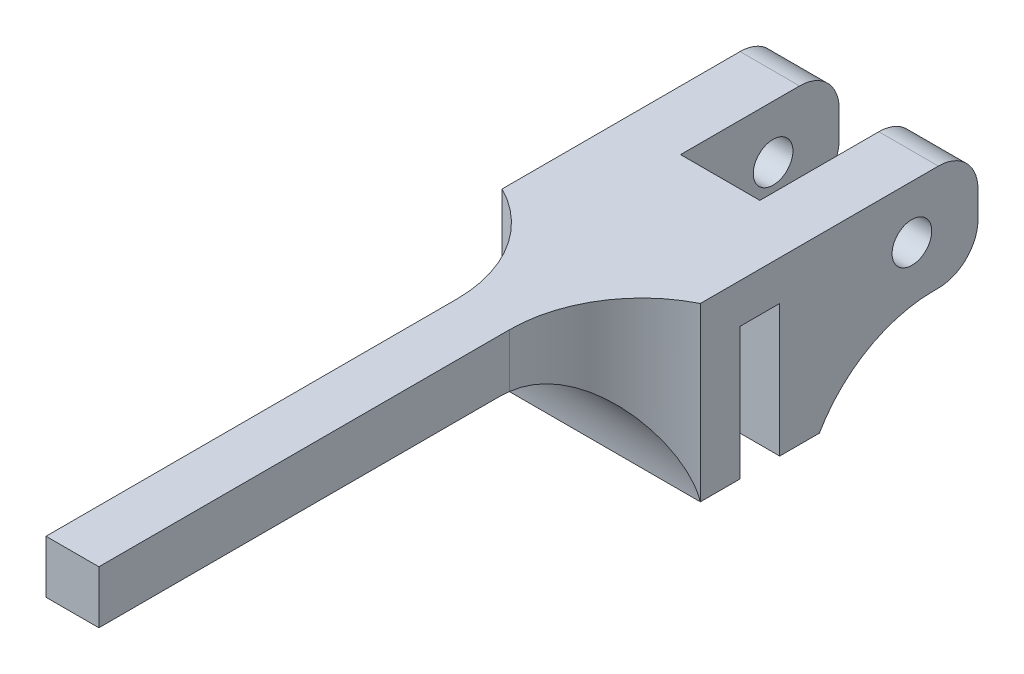
SolidWorks part; units mm, degrees
ref_plane "Alzado" through (0, 0, 0) normal (0, 0, 1) x (1, 0, 0)
ref_plane "Planta" through (0, 0, 0) normal (0, 1, 0) x (1, 0, 0)
ref_plane "Vista lateral" through (0, 0, 0) normal (1, 0, 0) x (0, 0, -1)
sketch "Croquis2" plane through (0, 0, 0) normal (0, 0, 1) x (1, 0, 0)
  line L1 (-7.5, 6.5) -> (7.5, 6.5)
  line L2 (-7.5, 6.5) -> (-7.5, -6.5)
  line L3 (-7.5, -6.5) -> (7.5, -6.5)
  line L4 (7.5, 6.5) -> (7.5, -6.5)
  point P4 (0, -6.5)
  point P6 (7.5, 0)
  dimension "D1" = 15
  dimension "D2" = 13
extrude "Saliente-Extruir1" add sketch "Croquis2" along normal mid plane 9
sketch "Croquis3" plane through (0, 0, 0) normal (0, 0, 1) x (1, 0, 0)
  line L0 (-7.5, 6.5) -> (-7.5, -6.5) construction
  line L1 (-7.5, 3.5) -> (7.5, 3.5)
  line L2 (-7.5, 3.5) -> (-7.5, -6.5)
  line L3 (-7.5, -6.5) -> (7.5, -6.5)
  line L4 (7.5, 3.5) -> (7.5, -6.5)
  line L5 (7.5, 6.5) -> (-7.5, 6.5) construction
  dimension "D1" = 3
extrude "Cortar-Extruir1" cut sketch "Croquis3" against normal mid plane 3
sketch "Croquis4" plane through (0, 0, 0) normal (0, 0, 1) x (1, 0, 0)
  line L0 (7.5, 6.5) -> (-7.5, 6.5) construction
  line L1 (-1.5, 0) -> (-1.5, -6.5)
  line L2 (-7.5, -6.5) -> (7.5, -6.5) construction
  line L3 (1.5, 0) -> (1.5, -6.5)
  line L4 (-1.5, -6.5) -> (1.5, -6.5)
  arc A0 (1.5, 0) -> (-1.5, 0) centre (0, 0) ccw
  dimension "D2" = 3
  dimension "D1" = 6.5
extrude "Cortar-Extruir2" cut sketch "Croquis4" against normal through all
sketch "Croquis5" plane through (0, 0, -4.5) normal (0, 0, -1) x (-1, 0, 0)
  line L1 (-3, -1.5) -> (3, -1.5) construction
  line L2 (-3, -1.5) -> (-3, 6.5) construction
  line L3 (-3, 6.5) -> (3, 6.5) construction
  line L4 (3, -1.5) -> (3, 6.5) construction
  line L6 (-3, 6.5) -> (-7.5, 6.5)
  line L7 (-3, 6.5) -> (-3, -1.5)
  line L8 (-3, -1.5) -> (-7.5, -1.5)
  line L9 (-7.5, 6.5) -> (-7.5, -1.5)
  line L10 (3, 6.5) -> (7.5, 6.5)
  line L11 (3, 6.5) -> (3, -1.5)
  line L12 (3, -1.5) -> (7.5, -1.5)
  line L13 (7.5, 6.5) -> (7.5, -1.5)
  line L14 (-7.5, 6.5) -> (7.5, 6.5) construction
  point P6 (0, 6.5)
  dimension "D1" = 6
  dimension "D2" = 8
  dimension "D3" = 4.5
extrude "Saliente-Extruir2" add sketch "Croquis5" along normal blind 12
sketch "Croquis7" plane through (0, 0, 0) normal (1, 0, 0) x (0, 0, -1)
  line L0 (16.5, -1.5) -> (16.5, 6.5) construction
  line L3 (16.5, 6.5) -> (16.5, -1.5) construction
  circle A0 centre (11.5, 2.5) radius 1.5
  point P12 (16.5, 2.5)
  dimension "D1" = 3
  dimension "D2" = 5
extrude "Cortar-Extruir3" cut sketch "Croquis7" against normal through all both and the other way through all
fillet "Redondeo2" radius 3 4 edges at (-5.25, -1.5, -16.5) (-5.25, 6.5, -16.5) (5.25, 6.5, -16.5) (5.25, -1.5, -16.5)
fillet "Redondeo3" radius 10 2 edges at (-5.25, -1.5, -4.5) (5.25, -1.5, -4.5)
fillet "Redondeo4" radius 0.5 3 edges at (1.5, -3.25, -4.5) (0, 1.5, -4.5) (-1.5, -3.25, -4.5)
sketch "Croquis8" plane through (0, 0, 4.5) normal (0, 0, 1) x (1, 0, 0)
  line L0 (7.5, 6.5) -> (-7.5, 6.5) construction
  line L1 (-2, 6.5) -> (2, 6.5)
  line L2 (-2, 6.5) -> (-2, 2.5)
  line L3 (-2, 2.5) -> (2, 2.5)
  line L4 (2, 6.5) -> (2, 2.5)
  point P6 (0, 2.5)
  dimension "D1" = 4
  dimension "D2" = 4
extrude "Saliente-Extruir3" add sketch "Croquis8" along normal blind 40
fillet "Redondeo5" radius 10 3 edges at (0, 2.5, 4.5) (-2, 4.5, 4.5) (2, 4.5, 4.5)
